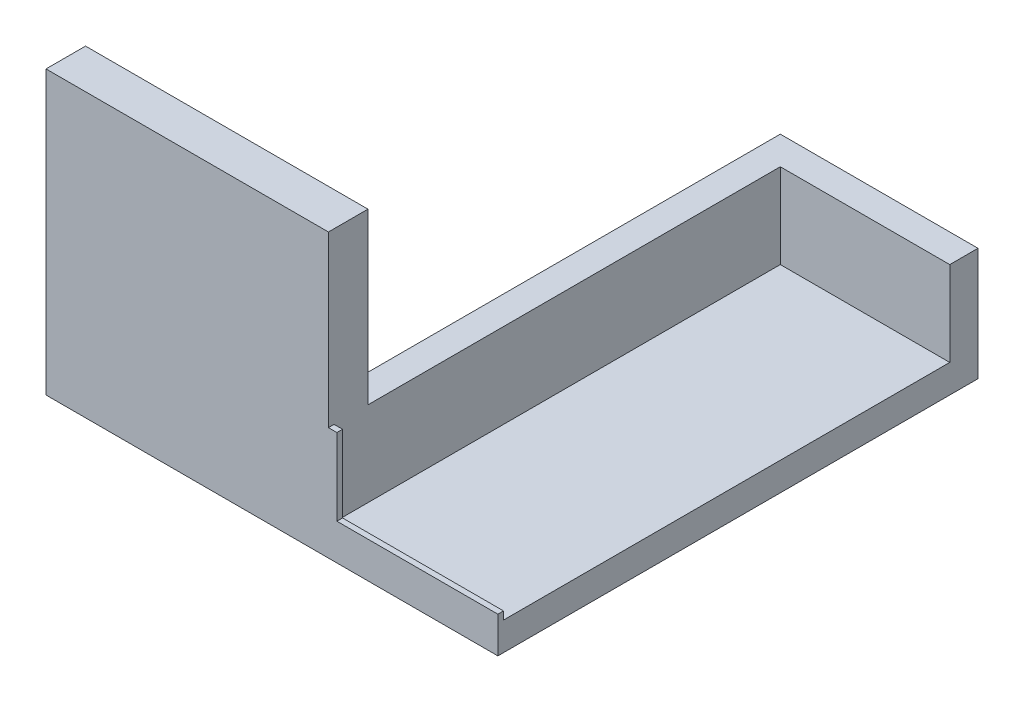
SolidWorks part; units mm, degrees
ref_plane "Ebene vorne" through (0, 0, 0) normal (0, 0, 1) x (1, 0, 0)
ref_plane "Ebene oben" through (0, 0, 0) normal (0, 1, 0) x (1, 0, 0)
ref_plane "Ebene rechts" through (0, 0, 0) normal (1, 0, 0) x (0, 0, -1)
sketch "Sketch1" plane through (0, 0, 0) normal (0, 1, 0) x (1, 0, 0)
  line L1 (-30, 80) -> (0, 80)
  line L2 (-30, 80) -> (-30, 0)
  line L3 (-30, 0) -> (0, 0)
  line L4 (0, 80) -> (0, 0)
  line L5 (0, 80) -> (-35, 80)
  line L6 (0, 80) -> (0, 85)
  line L7 (0, 85) -> (-35, 85)
  line L8 (-35, 80) -> (-35, 85)
  line L9 (-30, 80) -> (-35, 80)
  line L10 (-30, 80) -> (-30, 7)
  line L11 (-30, 7) -> (-35, 7)
  line L12 (-35, 80) -> (-35, 7)
  line L13 (-30, 7) -> (-80, 7)
  line L14 (-30, 7) -> (-30, 0)
  line L15 (-30, 0) -> (-80, 0)
  line L16 (-80, 7) -> (-80, 0)
  point P11 (0, 0)
  point P12 (0, 0)
  dimension "D1" = 30
  dimension "D2" = 80
  dimension "D3" = 5
  dimension "D4" = 35
  dimension "D5" = 7
  dimension "D6" = 50
extrude "Boss-Extrude1" add sketch "Sketch1" along normal blind 5 contours L4 L1 L2 L3 region at (-15, 0, -40)
extrude "Boss-Extrude2" add sketch "Sketch1<3>" along normal blind 20 contours L5 L12 L11 L2 | L8 L5 L7 | L6 L5 L8 L7 region at (-17.5, 0, -82.5) region at (-32.5, 0, -43.5)
sketch "Sketch1<3>" plane through (0, 0, 0) normal (0, 1, 0) x (1, 0, 0) same geometry as "Sketch1"
extrude "Boss-Extrude3" add sketch "Sketch1<4>" along normal blind 50 contours L13 L16 L15 L2 L11 region at (-55, 0, -3.5)
sketch "Sketch1<4>" plane through (0, 0, 0) normal (0, 1, 0) x (1, 0, 0) same geometry as "Sketch1"
sketch "Sketch2" plane through (0, 5, 0) normal (0, 1, 0) x (1, 0, 0)
  line L0 (-30, 80) -> (-30, 0) construction
  line L1 (0, 0) -> (-30, 0)
  line L2 (0, 0) -> (0, 1)
  line L3 (0, 1) -> (-30, 1)
  line L4 (-30, 0) -> (-30, 1)
  line L6 (-30, 0) -> (-28.5, 0)
  line L7 (-30, 0) -> (-30, 1)
  line L8 (-30, 1) -> (-28.5, 1)
  line L9 (-28.5, 0) -> (-28.5, 1)
  line M1 (0, 0) -> (0, 80)
  line M3 (-30, 80) -> (-30, 0)
  line M4 (-30, 0) -> (0, 0)
  dimension "D1" = 1
  dimension "D2" = 1.5
extrude "Boss-Extrude4" add sketch "Sketch2" along normal blind 1.4 contours L9 L1 L3 M1 region at (-14.25, 5, -0.5)
extrude "Boss-Extrude5" add sketch "Sketch2<3>" along normal blind 15 contours L9 L3 M4 M3 region at (-29.25, 5, -0.5)
sketch "Sketch2<3>" plane through (0, 5, 0) normal (0, 1, 0) x (1, 0, 0) same geometry as "Sketch2"
